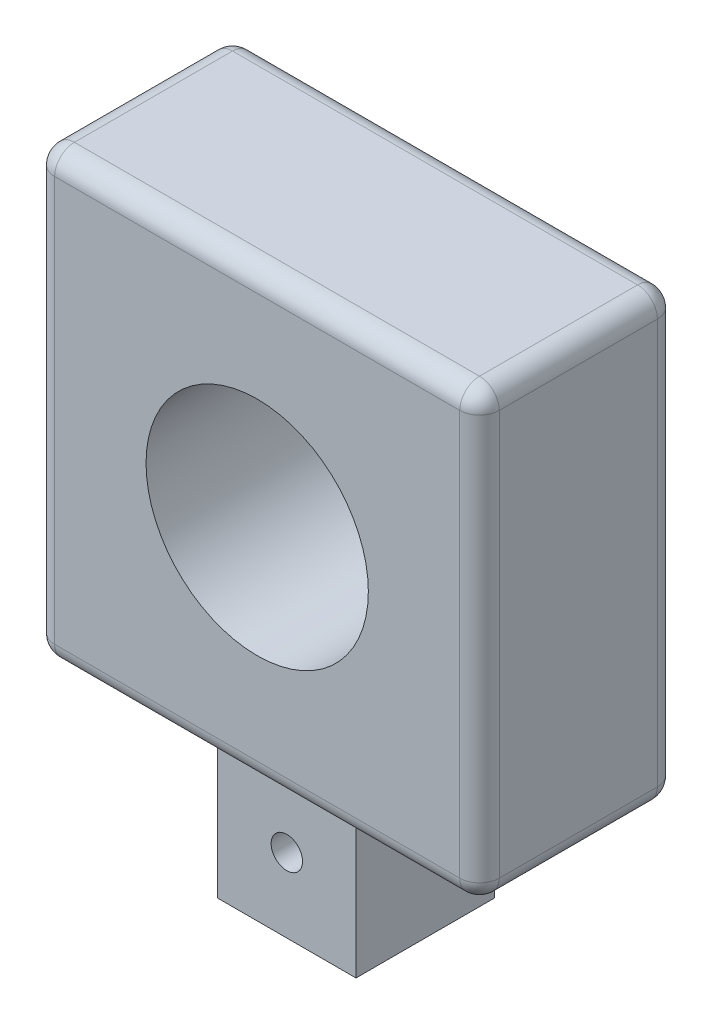
SolidWorks part; units mm, degrees
ref_plane "Front Plane" through (0, 0, 0) normal (0, 0, 1) x (1, 0, 0)
ref_plane "Top Plane" through (0, 0, 0) normal (0, 1, 0) x (1, 0, 0)
ref_plane "Right Plane" through (0, 0, 0) normal (1, 0, 0) x (0, 0, -1)
sketch "Sketch1" plane through (0, 0, 0) normal (0, 1, 0) x (1, 0, 0)
  line L1 (-8.89, -8.89) -> (8.89, -8.89)
  line L2 (-8.89, -8.89) -> (-8.89, 8.89)
  line L3 (-8.89, 8.89) -> (8.89, 8.89)
  line L4 (8.89, -8.89) -> (8.89, 8.89)
  line L5 (-8.89, -8.89) -> (8.89, 8.89) construction
  line L6 (-8.89, 8.89) -> (8.89, -8.89) construction
  point P0 (0, 0)
  dimension "D1" = 17.78
  dimension "D2" = 17.78
extrude "Boss-Extrude1" add sketch "Sketch1" along normal blind 12.7 and the other way blind 6.35
sketch "Sketch2" plane through (0, 12.7, 0) normal (0, 1, 0) x (1, 0, 0)
  line L1 (-28.575, -12.7) -> (28.575, -12.7)
  line L2 (-28.575, -12.7) -> (-28.575, 12.7)
  line L3 (-28.575, 12.7) -> (28.575, 12.7)
  line L4 (28.575, -12.7) -> (28.575, 12.7)
  line L5 (-28.575, -12.7) -> (28.575, 12.7) construction
  line L6 (-28.575, 12.7) -> (28.575, -12.7) construction
  point P0 (0, 0)
  dimension "D1" = 57.15
  dimension "D2" = 25.4
extrude "Boss-Extrude2" add sketch "Sketch2" along normal blind 57.15
sketch "Sketch3" plane through (0, 0, 12.7) normal (0, 0, 1) x (1, 0, 0)
  line L0 (-28.575, 69.85) -> (28.575, 69.85) construction
  line L1 (28.575, 69.85) -> (28.575, 12.7) construction
  circle A0 centre (0, 41.275) radius 14.2875
  dimension "D1" = 28.575
  dimension "D2" = 28.575
  dimension "D3" = 28.575
extrude "Cut-Extrude1" cut sketch "Sketch3" against normal through all
fillet "Fillet1" radius 2.54 12 edges at (28.575, 69.85, 0) (28.575, 12.7, 0) (-28.575, 69.85, 0) (-28.575, 12.7, 0) (28.575, 41.275, -12.7) (0, 69.85, -12.7) (-28.575, 41.275, -12.7) (0, 12.7, -12.7) (-28.575, 41.275, 12.7) (0, 69.85, 12.7) (28.575, 41.275, 12.7) (0, 12.7, 12.7)
sketch "Sketch4" plane through (0, 0, -8.89) normal (0, 0, -1) x (-1, 0, 0)
  line L0 (-8.89, -6.35) -> (8.89, -6.35) construction
  line L1 (-8.89, -6.35) -> (-8.89, 12.7) construction
  circle A0 centre (0, 3.175) radius 2.0193
  dimension "D1" = 4.0386
  dimension "D2" = 9.525
  dimension "D3" = 8.89
extrude "Cut-Extrude2" cut sketch "Sketch4" against normal through all
